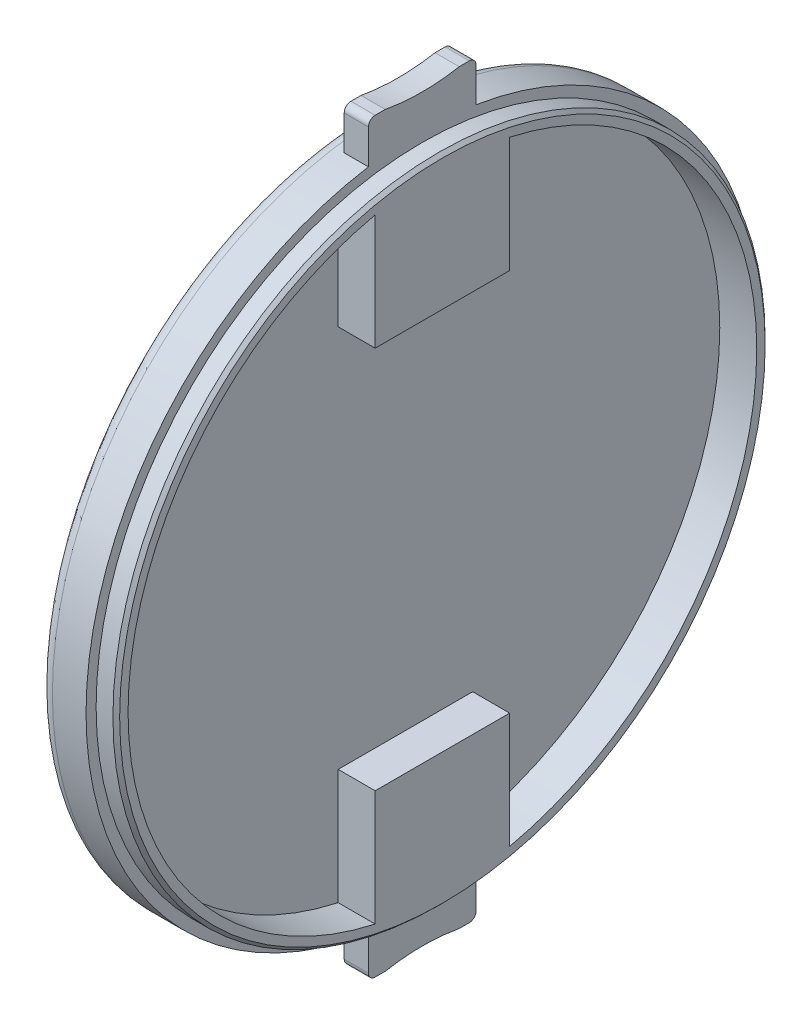
SolidWorks part; units mm, degrees
ref_plane "Plan de face" through (0, 0, 0) normal (0, 0, 1) x (1, 0, 0)
ref_plane "Plan de dessus" through (0, 0, 0) normal (0, 1, 0) x (1, 0, 0)
ref_plane "Plan de droite" through (0, 0, 0) normal (1, 0, 0) x (0, 0, -1)
sketch "Esquisse1" plane through (0, 0, 0) normal (0, 0, 1) x (1, 0, 0)
  line L0 (0, 0) -> (-37.1408, 0) construction
  line L1 (0, 0) -> (0, 46.75)
  line L2 (0, 46.75) -> (5.5, 46.75)
  line L3 (5.5, 46.75) -> (5.5, 48.5)
  line L4 (5.5, 48.5) -> (2.5, 48.5)
  line L5 (2.5, 48.5) -> (2.5, 50)
  line L6 (2.5, 50) -> (-2.5, 50)
  line L7 (-4.5, 48) -> (-4.5, 0)
  line L8 (0, 0) -> (-4.5, 0)
  line L11 (6.5, 48.5) -> (2.5, 48.5) construction
  line L13 (202.5, 50) -> (2.5, 50) construction
  arc A0 (-2.5, 50) -> (-4.5, 48) centre (-2.5, 48) ccw
  dimension "D5" = 2
  dimension "D1" = 3
  dimension "D2" = 1.75
  dimension "D3" = 10
  dimension "D4" = 5.5
revolve "Révolution1" add sketch "Esquisse1" angle 360 about L0
chamfer "Chanfrein1" distance 0.5 angle 45 1 edges at (5.5, 0, -48.5)
sketch "Esquisse2" plane through (0, 0, 0) normal (1, 0, 0) x (0, 0, -1)
  line L0 (-10, 45.668) -> (-10, 28.5)
  line L1 (10, 45.668) -> (10, 28.5)
  line L2 (-10, 28.5) -> (10, 28.5)
  line L3 (-10, -28.5) -> (10, -28.5)
  line L4 (-10, -28.5) -> (-10, -45.668)
  line L5 (10, -28.5) -> (10, -45.668)
  arc A0 (-10, -45.668) -> (10, -45.668) centre (0, 0) ccw
  circle A1 centre (0, 0) radius 46.75
  arc A2 (10, 45.668) -> (-10, 45.668) centre (0, 0) ccw
  dimension "D2" = 20
  dimension "D3" = 10
  dimension "D4" = 57
  dimension "D5" = 28.5
  dimension "D1" = 0
extrude "Boss.-Extru.1" add sketch "Esquisse2" along normal up to surface (5.5 mm away) up to face at (5.5, 0, -48)
sketch "Esquisse3" plane through (2.5, 0, 0) normal (1, 0, 0) x (0, 0, -1)
  line L0 (-8, 54.5) -> (-8, 49.3559)
  line L1 (8, 54.5) -> (8, 49.3559)
  line L2 (-7, 55.5) -> (-5.5, 55.5)
  line L3 (5.5, 55.5) -> (7, 55.5)
  circle A0 centre (0, 0) radius 50 construction
  arc A1 (8, 49.3559) -> (-8, 49.3559) centre (0, 0) ccw
  arc A2 (-5.5, 55.5) -> (5.5, 55.5) centre (0, 85.5) ccw
  arc A3 (8, 54.5) -> (7, 55.5) centre (7, 54.5) ccw
  arc A4 (-7, 55.5) -> (-8, 54.5) centre (-7, 54.5) ccw
  dimension "D4" = 1
  dimension "D1" = 16
  dimension "D2" = 8
  dimension "D3" = 55.5
extrude "Boss.-Extru.2" add sketch "Esquisse3" against normal blind 3.6
ref_axis "Axe1" through (-2.5, 0, 0) along (1, 0, 0)
pattern_circular "Répétition circulaire1" count 2 over 360 about axis through (-2.5, 0, 0) along (1, 0, 0) of "Boss.-Extru.2"
